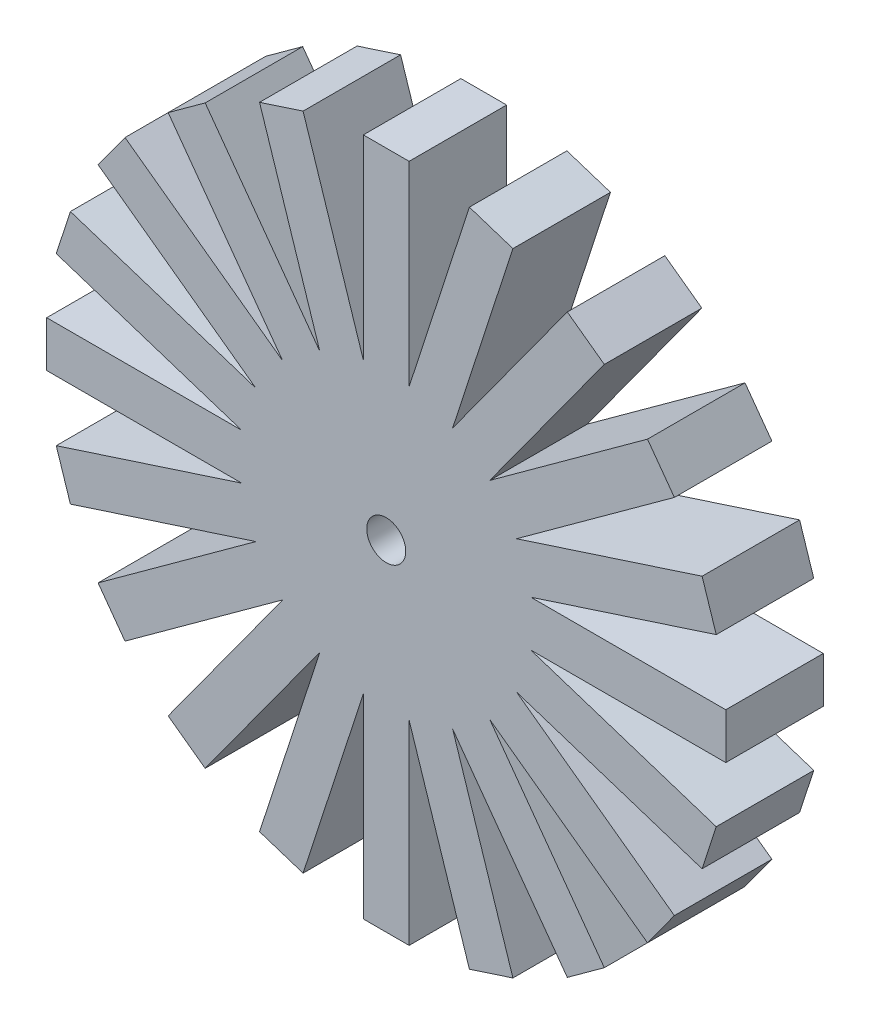
SolidWorks part; units mm, degrees
ref_plane "Plan de face" through (0, 0, 0) normal (0, 0, 1) x (1, 0, 0)
ref_plane "Plan de dessus" through (0, 0, 0) normal (0, 1, 0) x (1, 0, 0)
ref_plane "Plan de droite" through (0, 0, 0) normal (1, 0, 0) x (0, 0, -1)
sketch "Esquisse1" plane through (0, 0, 0) normal (0, 0, 1) x (1, 0, 0)
  line L0 (0, 15) -> (0, -15) construction
  line L1 (-15, 0) -> (15, 0) construction
  line L2 (-14.8153, -2.3465) -> (-34.8153, -2.3465)
  line L3 (-34.8153, -2.3465) -> (-34.8153, 2.3465)
  line L4 (-14.8153, 2.3465) -> (-34.8153, 2.3465)
  line L5 (0, 0) -> (-14.8153, 2.3465) construction
  line L6 (-13.3651, 6.8099) -> (-32.3862, 12.9902)
  line L7 (-33.8365, 8.5269) -> (-32.3862, 12.9902)
  line L8 (-14.8153, 2.3465) -> (-33.8365, 8.5269)
  line L9 (-10.6066, 10.6066) -> (-26.7869, 22.3623)
  line L10 (-29.5454, 18.5656) -> (-26.7869, 22.3623)
  line L11 (-13.3651, 6.8099) -> (-29.5454, 18.5656)
  line L12 (-6.8099, 13.3651) -> (-18.5656, 29.5454)
  line L13 (-22.3623, 26.7869) -> (-18.5656, 29.5454)
  line L14 (-10.6066, 10.6066) -> (-22.3623, 26.7869)
  line L15 (-2.3465, 14.8153) -> (-8.5269, 33.8365)
  line L16 (-12.9902, 32.3862) -> (-8.5269, 33.8365)
  line L17 (-6.8099, 13.3651) -> (-12.9902, 32.3862)
  line L18 (2.3465, 14.8153) -> (2.3465, 34.8153)
  line L19 (-2.3465, 34.8153) -> (2.3465, 34.8153)
  line L20 (-2.3465, 14.8153) -> (-2.3465, 34.8153)
  line L21 (6.8099, 13.3651) -> (12.9902, 32.3862)
  line L22 (8.5269, 33.8365) -> (12.9902, 32.3862)
  line L23 (2.3465, 14.8153) -> (8.5269, 33.8365)
  line L24 (10.6066, 10.6066) -> (22.3623, 26.7869)
  line L25 (18.5656, 29.5454) -> (22.3623, 26.7869)
  line L26 (6.8099, 13.3651) -> (18.5656, 29.5454)
  line L27 (13.3651, 6.8099) -> (29.5454, 18.5656)
  line L28 (26.7869, 22.3623) -> (29.5454, 18.5656)
  line L29 (10.6066, 10.6066) -> (26.7869, 22.3623)
  line L30 (14.8153, 2.3465) -> (33.8365, 8.5269)
  line L31 (32.3862, 12.9902) -> (33.8365, 8.5269)
  line L32 (13.3651, 6.8099) -> (32.3862, 12.9902)
  line L33 (14.8153, -2.3465) -> (34.8153, -2.3465)
  line L34 (34.8153, 2.3465) -> (34.8153, -2.3465)
  line L35 (14.8153, 2.3465) -> (34.8153, 2.3465)
  line L36 (13.3651, -6.8099) -> (32.3862, -12.9902)
  line L37 (33.8365, -8.5269) -> (32.3862, -12.9902)
  line L38 (14.8153, -2.3465) -> (33.8365, -8.5269)
  line L39 (10.6066, -10.6066) -> (26.7869, -22.3623)
  line L40 (29.5454, -18.5656) -> (26.7869, -22.3623)
  line L41 (13.3651, -6.8099) -> (29.5454, -18.5656)
  line L42 (6.8099, -13.3651) -> (18.5656, -29.5454)
  line L43 (22.3623, -26.7869) -> (18.5656, -29.5454)
  line L44 (10.6066, -10.6066) -> (22.3623, -26.7869)
  line L45 (2.3465, -14.8153) -> (8.5269, -33.8365)
  line L46 (12.9902, -32.3862) -> (8.5269, -33.8365)
  line L47 (6.8099, -13.3651) -> (12.9902, -32.3862)
  line L48 (-2.3465, -14.8153) -> (-2.3465, -34.8153)
  line L49 (2.3465, -34.8153) -> (-2.3465, -34.8153)
  line L50 (2.3465, -14.8153) -> (2.3465, -34.8153)
  line L51 (-6.8099, -13.3651) -> (-12.9902, -32.3862)
  line L52 (-8.5269, -33.8365) -> (-12.9902, -32.3862)
  line L53 (-2.3465, -14.8153) -> (-8.5269, -33.8365)
  line L54 (-10.6066, -10.6066) -> (-22.3623, -26.7869)
  line L55 (-18.5656, -29.5454) -> (-22.3623, -26.7869)
  line L56 (-6.8099, -13.3651) -> (-18.5656, -29.5454)
  line L57 (-13.3651, -6.8099) -> (-29.5454, -18.5656)
  line L58 (-26.7869, -22.3623) -> (-29.5454, -18.5656)
  line L59 (-10.6066, -10.6066) -> (-26.7869, -22.3623)
  line L60 (-14.8153, -2.3465) -> (-33.8365, -8.5269)
  line L61 (-32.3862, -12.9902) -> (-33.8365, -8.5269)
  line L62 (-13.3651, -6.8099) -> (-32.3862, -12.9902)
  circle A0 centre (0, 0) radius 15
  circle A1 centre (0, 0) radius 2
  point P12 (-34.8153, 0)
  dimension "D1" = 30
  dimension "D5" = 4
  dimension "D2" = 9
  dimension "D3" = 20
  dimension "D4" = 20
extrude "Boss.-Extru.1" add sketch "Esquisse1" along normal blind 10 contours A0 L4 L3 L2 | A0 | A0 | A0 | A0 | A0 | A0 | A0 | A0 | A0 | A0 | A0 L6 L7 L8 | A0 L60 L61 L62 | A0 L54 L55 L56 | A0 L48 L49 L50 | A0 L42 L43 L44 | A0 L36 L37 L38 | A0 L30 L31 L32 | A0 L24 L25 L26 | A0 L18 L19 L20 | A0 L12 L13 L14 region at (-23.6593, -7.6874, 0) region at (-24.8769, 0, 0) region at (-14.5757, 0, 0) region at (-23.6593, 7.6874, 0) region at (-20.1258, -14.6223, 0) region at (-20.1258, 14.6223, 0) region at (-14.6223, -20.1258, 0) region at (-14.6223, 20.1258, 0) region at (-7.6874, -23.6593, 0) region at (-7.6874, 23.6593, 0) region at (0, -24.8769, 0) region at (0, 24.8769, 0) region at (7.6874, -23.6593, 0) region at (7.6874, 23.6593, 0) region at (14.6223, -20.1258, 0) region at (14.6223, 20.1258, 0) region at (20.1258, -14.6223, 0) region at (20.1258, 14.6223, 0) region at (23.6593, -7.6874, 0) region at (23.6593, 7.6874, 0) region at (24.8769, 0, 0)
